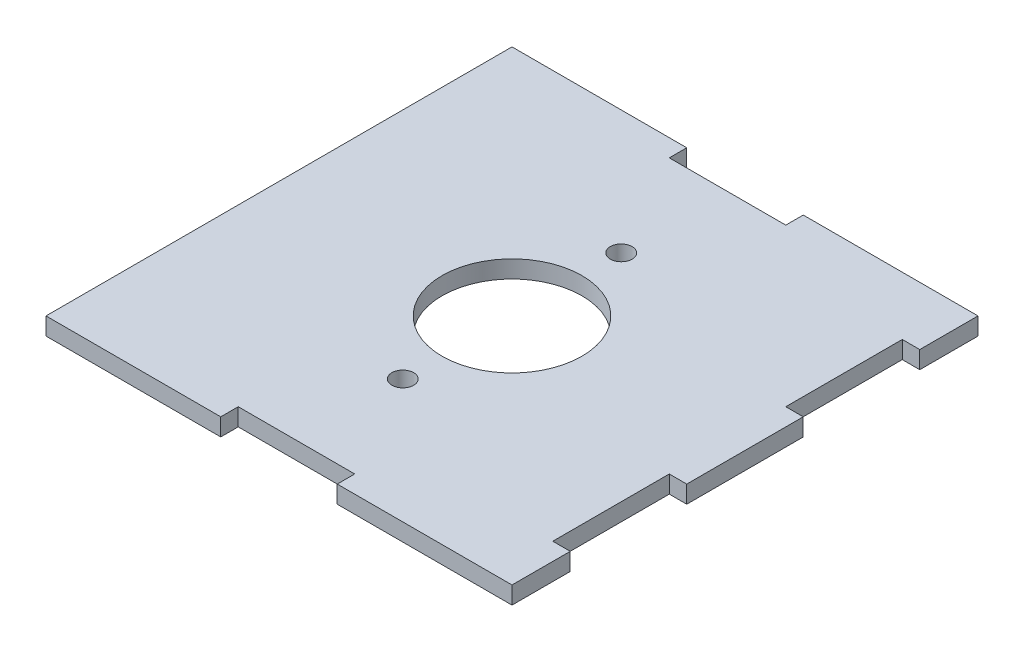
SolidWorks part; units mm, degrees
ref_plane "Alzado" through (0, 0, 0) normal (0, 0, 1) x (1, 0, 0)
ref_plane "Planta" through (0, 0, 0) normal (0, 1, 0) x (1, 0, 0)
ref_plane "Vista lateral" through (0, 0, 0) normal (1, 0, 0) x (0, 0, -1)
sketch "Croquis1" plane through (0, 0, 0) normal (0, 1, 0) x (1, 0, 0)
  line L0 (0, 0) -> (0, 18.75) construction
  line L1 (-40, 40) -> (-10, 40)
  line L2 (-40, 40) -> (-40, -40)
  line L3 (-40, -40) -> (-10, -40)
  line L4 (37, 30) -> (40, 30)
  line L5 (-40, 40) -> (40, -40) construction
  line L6 (-40, -40) -> (40, 40) construction
  line L7 (0, 0) -> (0, -18.75) construction
  line L49 (10, -40) -> (37, -40)
  line L50 (40, -30) -> (40, -40)
  line L51 (37, -10) -> (37, -30)
  line L52 (40, 10) -> (37, 10)
  line L53 (37, 40) -> (40, 40)
  line L54 (40, 10) -> (40, -10)
  line L55 (37, -10) -> (40, -10)
  line L56 (40, -30) -> (37, -30)
  line L58 (0, 37) -> (-10, 37)
  line L59 (0, 37) -> (10, 37)
  line L60 (10, 37) -> (10, 40)
  line L61 (-10, 37) -> (-10, 40)
  line L62 (10, 40) -> (37, 40)
  line L63 (-10, -37) -> (-10, -40)
  line L64 (10, -37) -> (10, -40)
  line L65 (0, -37) -> (10, -37)
  line L66 (0, -37) -> (-10, -37)
  line L68 (40, 40) -> (40, 30)
  line L69 (40, -40) -> (37, -40)
  line L70 (37, 30) -> (37, 10)
  circle A0 centre (0, 0) radius 12
  circle A1 centre (0, 18.75) radius 1.875
  circle A2 centre (0, -18.75) radius 1.875
  dimension "D3" = 24
  dimension "D6" = 3.75
  dimension "D7" = 3.75
  dimension "D1" = 80
  dimension "D2" = 80
  dimension "D4" = 18.75
  dimension "D5" = 18.75
  dimension "D16" = 10
  dimension "D17" = 10
extrude "Saliente-Extruir1" add sketch "Croquis1" along normal blind 3
